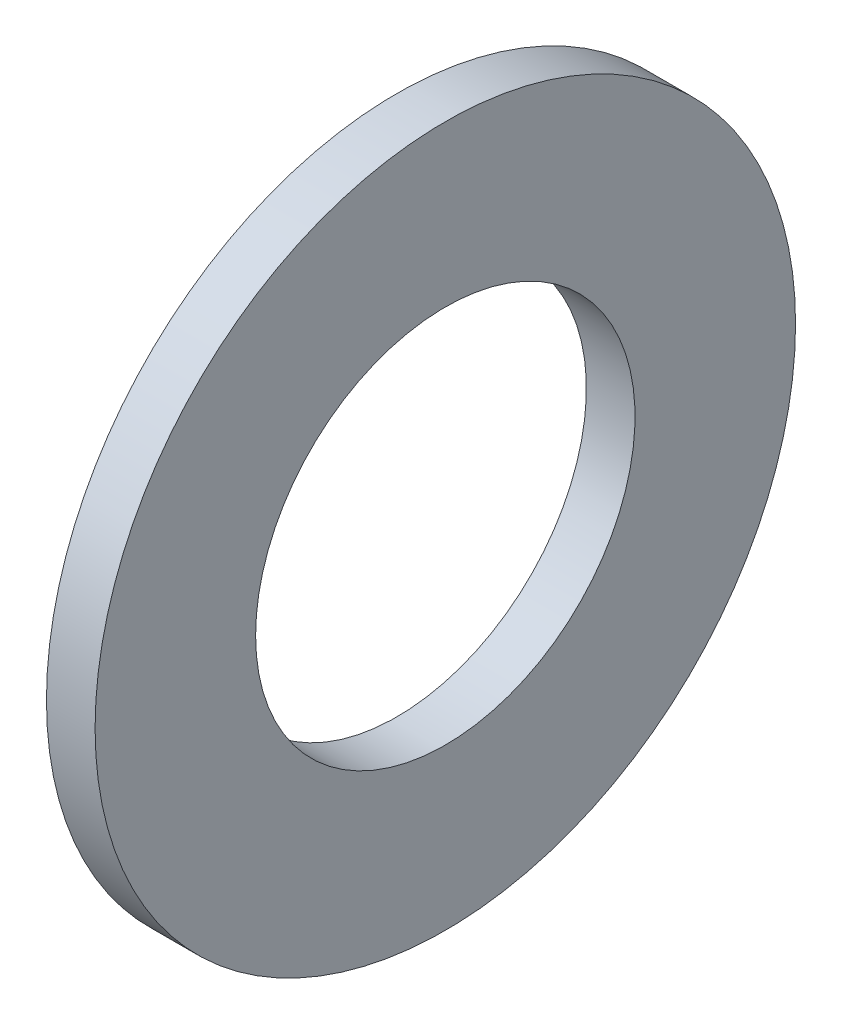
SolidWorks part; units mm, degrees
ref_plane "Plane1" through (0, 0, 0) normal (0, 0, 1) x (1, 0, 0)
ref_plane "Plane2" through (0, 0, 0) normal (0, 1, 0) x (1, 0, 0)
ref_plane "Plane3" through (0, 0, 0) normal (1, 0, 0) x (0, 0, -1)
sketch "Sketch1" plane through (0, 0, 0) normal (0, 0, 1) x (1, 0, 0)
  line L0 (-34.925, 0) -> (9.525, 0) construction
  line L1 (0, 19.5) -> (0, 36)
  line L2 (0, 36) -> (-5, 36)
  line L3 (-5, 36) -> (-5, 19.5)
  line L4 (-5, 19.5) -> (0, 19.5)
  dimension "Thickness" = 5
  dimension "Inside_dia" = 39
  dimension "Outside_dia" = 72
revolve "Base-Revolve" add sketch "Sketch1" angle 360 about L0
